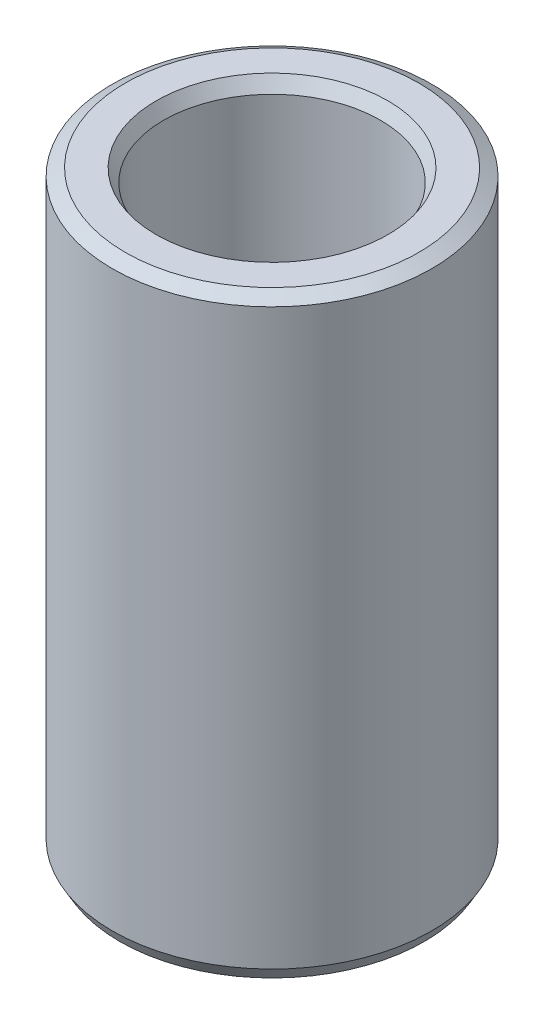
SolidWorks part; units mm, degrees
ref_plane "Front Plane" through (0, 0, 0) normal (0, 0, 1) x (1, 0, 0)
ref_plane "Top Plane" through (0, 0, 0) normal (0, 1, 0) x (1, 0, 0)
ref_plane "Right Plane" through (0, 0, 0) normal (1, 0, 0) x (0, 0, -1)
sketch "Sketch1" plane through (0, 0, 0) normal (0, 1, 0) x (1, 0, 0)
  circle A0 centre (0, 0) radius 60
  dimension "SLEEVE_OD" = 120
extrude "Boss-Extrude1" add sketch "Sketch1" along normal blind 223.0652
sketch "Sketch2" plane through (0, 0, 0) normal (0, 1, 0) x (1, 0, 0)
  circle A0 centre (0, 0) radius 40.7111
  dimension "BORE_D" = 81.4221
extrude "Cut-Extrude1" cut sketch "Sketch2" along normal through all
chamfer "Chamfer1" distance 2.8238 angle 60 4 edges at (0, 223.0652, 40.7111) (0, 0, 40.7111) (0, 0, 60) (0, 223.0652, 60) first distance on face at (0, 223.0652, 40.7111) first distance on face at (0, 0, 40.7111) first distance on face at (0, 223.0652, 60)
